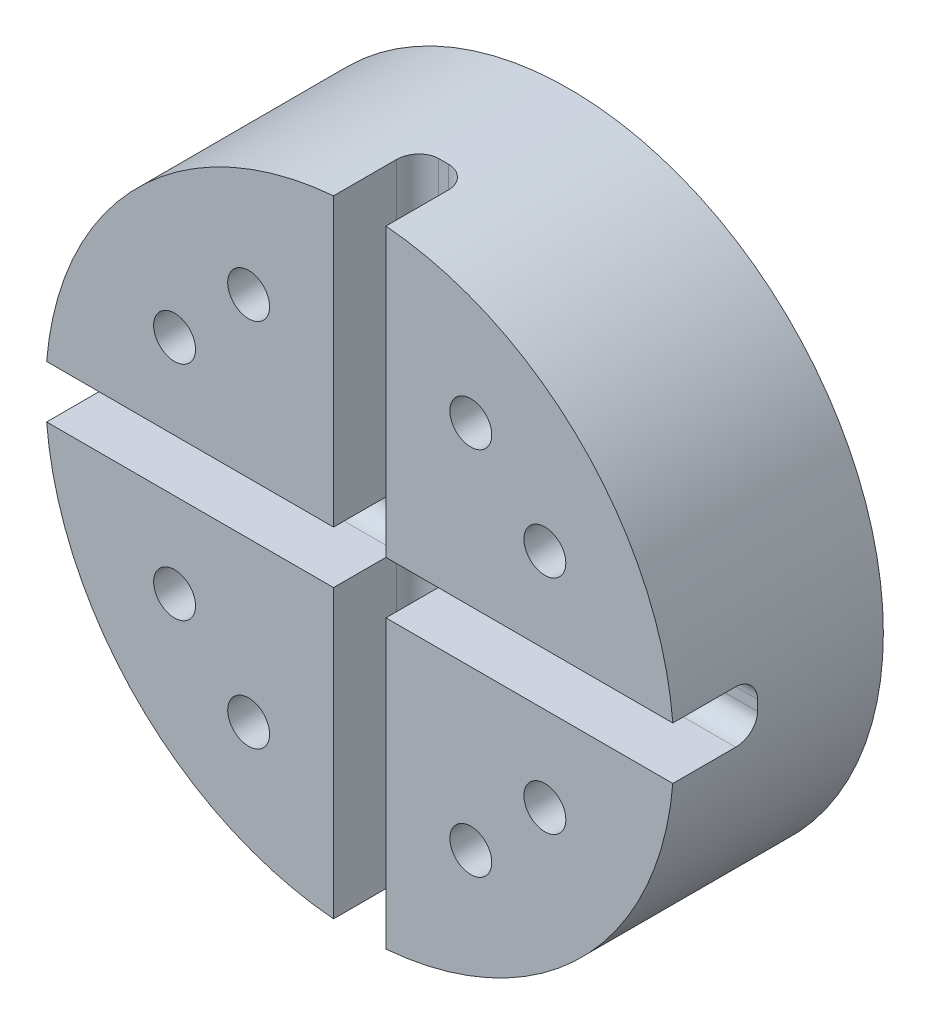
SolidWorks part; units mm, degrees
ref_plane "Front Plane" through (0, 0, 0) normal (0, 0, 1) x (1, 0, 0)
ref_plane "Top Plane" through (0, 0, 0) normal (0, 1, 0) x (1, 0, 0)
ref_plane "Right Plane" through (0, 0, 0) normal (1, 0, 0) x (0, 0, -1)
sketch "Sketch2" plane through (0, 0, 0) normal (0, 0, 1) x (1, 0, 0)
  circle A0 centre (0, 0) radius 15
  dimension "D1" = 30
extrude "Boss-Extrude1" add sketch "Sketch2" along normal blind 10
sketch "Sketch3" plane through (0, 0, 10) normal (0, 0, 1) x (1, 0, 0)
  line L5 (-1.25, 1.25) -> (-1.25, 15.296)
  line L6 (1.25, 1.25) -> (1.25, 15.296)
  line L7 (-1.25, 15.296) -> (1.25, 15.296)
  line L9 (1.25, 1.25) -> (15.6747, 1.25)
  line L10 (1.25, -1.25) -> (15.6747, -1.25)
  line L11 (15.6747, 1.25) -> (15.6747, -1.25)
  line L13 (1.25, -1.25) -> (1.25, -15.6292)
  line L14 (-1.25, -1.25) -> (-1.25, -15.6292)
  line L15 (1.25, -15.6292) -> (-1.25, -15.6292)
  line L17 (-1.25, 1.25) -> (-15.4105, 1.25)
  line L18 (-1.25, -1.25) -> (-15.4105, -1.25)
  line L19 (-15.4105, 1.25) -> (-15.4105, -1.25)
extrude "Cut-Extrude1" cut sketch "Sketch3" against normal blind 4
fillet "Fillet1" radius 1 8 edges at (-1.25, -8.0989, 6) (1.25, -8.0989, 6) (8.0989, -1.25, 6) (8.0989, 1.25, 6) (1.25, 8.0989, 6) (-1.25, 8.0989, 6) (-8.0989, -1.25, 6) (-8.0989, 1.25, 6)
sketch "Sketch4" plane through (0, 0, 10) normal (0, 0, 1) x (1, 0, 0)
  line L0 (0, 0) -> (-10.6066, 10.6066) construction
  line L1 (-5.3033, 5.3033) -> (-5.3033, 8.8388) construction
  line L2 (-5.3033, 5.3033) -> (-8.8388, 5.3033) construction
  line L6 (-8.8388, 5.3033) -> (-5.3033, 8.8388) construction
  arc A3 (-1.25, 14.9478) -> (-14.9478, 1.25) centre (0, 0) ccw construction
  circle A4 centre (-8.8388, 5.3033) radius 1
  circle A5 centre (-5.3033, 8.8388) radius 1
  dimension "D2" = 2
  dimension "D1" = 5
extrude "Cut-Extrude2" cut sketch "Sketch4" against normal up to surface (10 mm away) contours A5 | A4 region at (-5.3033, 8.8388, 10) up to face at (15, 0, 0)
pattern_circular "CirPattern1" count 4 every 90 about axis through (0, 0, 10) along (0, 0, -1) of "Cut-Extrude2"
